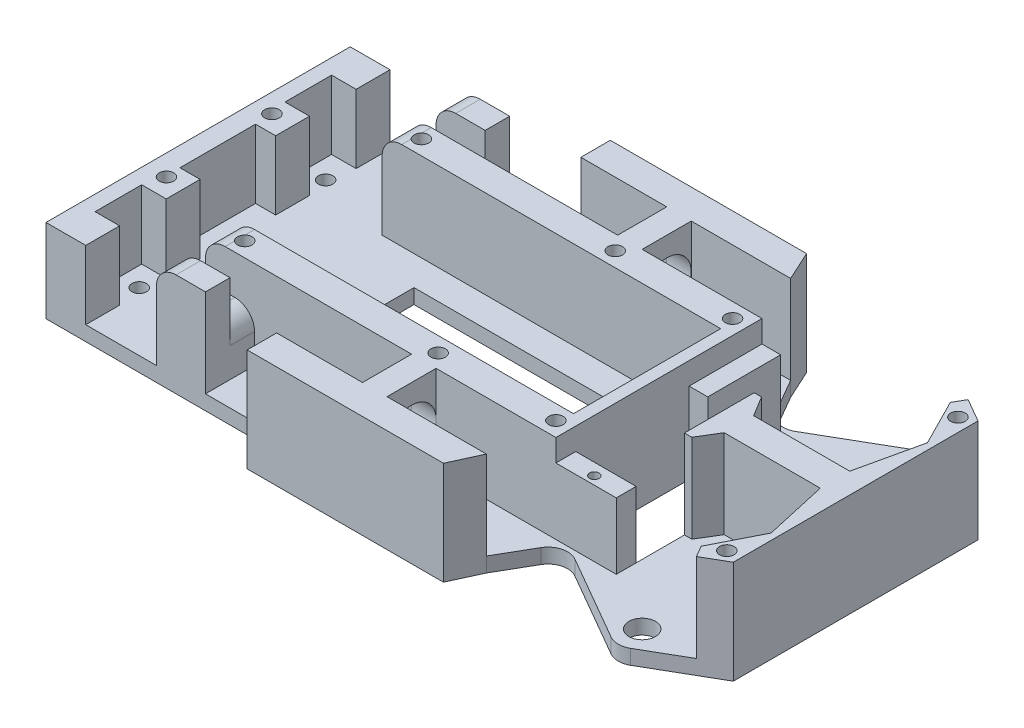
SolidWorks part; units mm, degrees
ref_plane "前视基准面" through (0, 0, 0) normal (0, 0, 1) x (1, 0, 0)
ref_plane "上视基准面" through (0, 0, 0) normal (0, 1, 0) x (1, 0, 0)
ref_plane "右视基准面" through (0, 0, 0) normal (1, 0, 0) x (0, 0, -1)
sketch "草图1" plane through (0, 0, 0) normal (0, 1, 0) x (1, 0, 0)
  line L0 (-67, 0) -> (67, 0) construction
  line L1 (-67, 31) -> (67, 31)
  line L2 (-67, 31) -> (-67, -31)
  line L3 (-67, -31) -> (67, -31)
  line L4 (67, 31) -> (67, -31)
  line L5 (-67, 31) -> (67, -31) construction
  line L6 (-67, -31) -> (67, 31) construction
  line L7 (0, -31) -> (0, 31) construction
  line L8 (22.7513, 31) -> (28.8135, 20.5)
  line L10 (-67, 1) -> (-67, -1)
  line L12 (67, 1) -> (67, -1)
  line L13 (-67, 1) -> (67, -1) construction
  line L14 (-67, -1) -> (67, 1) construction
  line L15 (-1, 31) -> (1, 31)
  line L17 (-1, -31) -> (1, -31)
  line L19 (-1, 31) -> (1, -31) construction
  line L20 (-1, -31) -> (1, 31) construction
  line L27 (28.8135, 20.5) -> (47, 31)
  line L28 (22.7513, -31) -> (28.8135, -20.5)
  line L29 (28.8135, -20.5) -> (47, -31)
  line L30 (56.5, -31) -> (67, -24.9378)
  line L31 (56.5, 31) -> (67, 24.9378)
  line L32 (56.5, 31) -> (51.75, 33.7424)
  line L33 (51.75, 33.7424) -> (47, 31)
  line L34 (51.75, -33.7424) -> (47, -31)
  line L35 (56.5, -31) -> (51.75, -33.7424)
  line L40 (26.9153, 6.15) -> (26.9153, -16.95)
  line L41 (26.9153, -16.95) -> (39.2153, -16.95)
  line L42 (39.2153, -16.95) -> (39.2153, 6.15)
  line L43 (39.2153, 6.15) -> (26.9153, 6.15)
  line L44 (26.9153, 6.15) -> (26.9153, -16.95)
  line L45 (26.9153, -16.95) -> (39.2153, -16.95)
  line L46 (39.2153, -16.95) -> (39.2153, 6.15)
  line L47 (39.2153, 6.15) -> (26.9153, 6.15)
  point P0 (0, 0)
  point P6 (0, 0)
  point P9 (0, 0)
  point P12 (0, 0)
  point P17 (0, 0)
  point P22 (0, 0)
  dimension "D1" = 134
  dimension "D2" = 62
  dimension "D7" = 6.15
  dimension "D8" = 30
  dimension "D9" = 20
  dimension "D10" = 90
  dimension "D11" = 21
  dimension "D12" = 30
  dimension "D13" = 10.5
  dimension "D14" = 30
  dimension "D15" = 30
  dimension "D16" = 0
extrude "凸台-拉伸1" add sketch "草图1" along normal blind 3 contours L1 L2 | L1 L4 | L3 L4 | L2 L1 L4 L3 region at (-2.8294, 0, -0.1991) region at (63.5, 0, -28.9793) region at (63.5, 0, 28.9793)
sketch "草图2" plane through (0, 3, 0) normal (0, 1, 0) x (1, 0, 0)
  line L0 (67, 31) -> (67, -31) construction
  line L1 (-67, 31) -> (67, 31) construction
  line L2 (67, 31) -> (67, -31) construction
  line L3 (-67, -31) -> (67, -31) construction
  circle A0 centre (51.5, 28) radius 2.7
  circle A1 centre (51.5, -28) radius 2.7
  dimension "D1" = 15.5
  dimension "D3" = 15.5
  dimension "D5" = 5.4
  dimension "D6" = 5.4
  dimension "D2" = 3
  dimension "D4" = 3
extrude "切除-拉伸1" cut sketch "草图2" against normal blind 4
extrude "凸台-拉伸3" add sketch "草图1<4>" along normal blind 3 contours L32 L33 L1 | L35 L3 L34 region at (51.75, 0, -31.9141) region at (51.75, 0, 31.9141)
sketch "草图1<4>" plane through (0, 0, 0) normal (0, 1, 0) x (1, 0, 0) same geometry as "草图1"
extrude "切除-拉伸4" cut sketch "草图1<6>" against normal blind 3 and the other way blind 4 contours L46 L47 L44 L45 | L8 L27 L1 | L1 L31 L4 | L29 L28 L3 | L30 L3 L4 region at (32.8549, 0, -27.5) region at (63.5, 0, -28.9793) region at (32.8549, 0, 27.5) region at (63.5, 0, 28.9793) region at (33.0653, 0, 5.4)
sketch "草图1<6>" plane through (0, 0, 0) normal (0, 1, 0) x (1, 0, 0) same geometry as "草图1"
sketch "草图3" plane through (0, 3, 0) normal (0, 1, 0) x (1, 0, 0)
  line L0 (-67, 0) -> (67, 0) construction
  line L1 (-67, 31) -> (-58.9, 31)
  line L2 (-67, 31) -> (-67, 7.7)
  line L3 (-67, 7.7) -> (-58.9, 7.7)
  line L4 (-58.9, 31) -> (-58.9, 7.7)
  line L5 (-67, -31) -> (-58.9, -31)
  line L6 (-67, -31) -> (-67, -7.7)
  line L7 (-67, -7.7) -> (-58.9, -7.7)
  line L8 (-58.9, -31) -> (-58.9, -7.7)
  line L9 (-67, 31) -> (-67, -31) construction
  line L10 (67, 24.9378) -> (67, -24.9378) construction
  line L12 (-58.9, 24.1) -> (-63.9, 24.1)
  line L13 (-58.9, 24.1) -> (-58.9, 14.6)
  line L14 (-58.9, 14.6) -> (-63.9, 14.6)
  line L15 (-63.9, 24.1) -> (-63.9, 14.6)
  line L16 (-58.9, -14.6) -> (-63.9, -14.6)
  line L17 (-58.9, -14.6) -> (-58.9, -24.1)
  line L18 (-58.9, -24.1) -> (-63.9, -24.1)
  line L19 (-63.9, -14.6) -> (-63.9, -24.1)
  line L20 (-67, 7.7) -> (-63, 7.7)
  line L21 (-67, 7.7) -> (-67, -7.7)
  line L22 (-67, -7.7) -> (-63, -7.7)
  line L23 (-63, 7.7) -> (-63, -7.7)
  line M12 (22.7513, 31) -> (-67, 31)
  line M13 (-67, 31) -> (-67, -31)
  line M14 (-67, -31) -> (22.7513, -31)
  dimension "D1" = 8.1
  dimension "D2" = 23.3
  dimension "D3" = 8.1
  dimension "D4" = 23.3
  dimension "D5" = 5
  dimension "D6" = 6.9
  dimension "D7" = 6.9
  dimension "D8" = 5
  dimension "D9" = 6.9
  dimension "D10" = 6.9
  dimension "D11" = 4
extrude "凸台-拉伸4" add sketch "草图3" along normal blind 14 contours L15 L12 L4 L3 L14 M12 M13 | L19 L16 L8 L7 L18 M13 M14 | L21 L20 L23 L22 region at (-62.95, 3, -30.7533) region at (-65, 3, 7.9467)
sketch "草图4" plane through (0, 3, 0) normal (0, 1, 0) x (1, 0, 0)
  line L0 (-67, 0) -> (67, 0) construction
  line L1 (67, 24.9378) -> (67, -24.9378) construction
  line L2 (-44.5, 9.7) -> (-44.5, 21) construction
  line L3 (-44.5, 21) -> (24.5, 21)
  line L4 (-44.5, 21) -> (-44.5, 15)
  line L5 (-44.5, 15) -> (24.5, 15)
  line L6 (24.5, 21) -> (24.5, 15)
  line L7 (-44.5, -15) -> (24.5, -15)
  line L8 (24.5, -21) -> (24.5, -15)
  line L9 (-44.5, -21) -> (24.5, -21)
  line L10 (-44.5, -21) -> (-44.5, -15)
  line L11 (26.9153, -21.7) -> (26.9153, -16.95) construction
  line L12 (24.5, 21) -> (26.9153, 21)
  line L13 (24.5, 21) -> (24.5, -21)
  line L14 (24.5, -21) -> (26.9153, -21)
  line L15 (26.9153, 21) -> (26.9153, -21)
  line L26 (-58.9, 31) -> (22.7513, 31) construction
  line L35 (-44.5, 31) -> (-34.5, 31)
  line L36 (-44.5, 31) -> (-44.5, 26)
  line L37 (-44.5, 26) -> (-34.5, 26)
  line L38 (-34.5, 31) -> (-34.5, 26)
  line L39 (-34.5, -21) -> (-39.5, -21)
  line L40 (-34.5, 26) -> (-39.5, 26)
  line L41 (-34.5, 26) -> (-34.5, 21)
  line L42 (-34.5, 21) -> (-39.5, 21)
  line L43 (-39.5, 26) -> (-39.5, 21)
  line L44 (-39.5, -26) -> (-39.5, -21)
  line L45 (-34.5, -26) -> (-39.5, -26)
  line L46 (-34.5, -26) -> (-34.5, -21)
  line L47 (-44.5, -26) -> (-34.5, -26)
  line L48 (-34.5, -31) -> (-34.5, -26)
  line L49 (-44.5, -31) -> (-34.5, -31)
  line L50 (-44.5, -31) -> (-44.5, -26)
  point P6 (0, 0)
  line M11 (26.9153, -16.95) -> (26.9153, 6.15)
  dimension "D1" = 15
  dimension "D2" = 6
  dimension "D3" = 69
  dimension "D4" = 5
  dimension "D5" = 10
  dimension "D6" = 5
  dimension "D7" = 5
extrude "凸台-拉伸5" add sketch "草图4" along normal blind 18 contours L13 L0 L15 L12 L6 | L6 L3 L4 L5 | L10 L9 L8 L7 | L0 L13 L8 L14 L15 M11 | L38 L35 L36 L37 | L41 L40 L43 L42 | L46 L39 L44 L45 | L48 L49 L50 L47 region at (25.7076, 3, -10.5) region at (25.7076, 3, 10.5) region at (-10, 3, -18) region at (-10, 3, 18)
fillet "圆角1" radius 4 4 edges at (51.75, 1.5, 33.7424) (51.75, 1.5, -33.7424) (28.8135, 1.5, -20.5) (28.8135, 1.5, 20.5)
sketch "草图5" plane through (0, 3, 0) normal (0, 1, 0) x (1, 0, 0)
  line L0 (-67, 0) -> (67, 0) construction
  line L1 (67, 24.9378) -> (67, -24.9378) construction
  line L2 (39.2153, 6.15) -> (39.2153, -16.95) construction
  line L3 (39.2153, 3) -> (67, 3)
  line L4 (39.2153, 3) -> (39.2153, -3)
  line L5 (39.2153, -3) -> (67, -3)
  line L6 (67, 3) -> (67, -3)
  line L7 (43.2153, 3) -> (40.7153, 7.103)
  line L8 (39.2153, 3) -> (43.2153, 3)
  line L9 (39.2153, 3) -> (39.2153, 7.103)
  line L10 (39.2153, 7.103) -> (43.2153, 7.103) construction
  line L11 (43.2153, 3) -> (43.2153, 7.103) construction
  line L12 (40.7153, 7.103) -> (39.2153, 7.103)
  line L13 (39.2153, -3) -> (39.2153, -7.103)
  line L14 (40.7153, -7.103) -> (39.2153, -7.103)
  line L15 (43.2153, -3) -> (40.7153, -7.103)
  line L16 (39.2153, -3) -> (43.2153, -3)
  point P6 (0, 0)
  line M11 (67, -24.9378) -> (67, 24.9378)
  line M37 (39.2153, 6.15) -> (39.2153, -16.95)
  dimension "D1" = 6
  dimension "D2" = 3
  dimension "D3" = 4
  dimension "D4" = 1.5
extrude "凸台-拉伸6" add sketch "草图5" along normal blind 18 contours L5 L3 M37 M11 | L7 L12 L9 L3 M37 | L15 L5 L14 M37 region at (40.6849, 3, -4.7406) region at (53.1076, 3, 0) region at (40.6849, 3, 4.7406)
sketch "草图6" plane through (0, 3, 0) normal (0, 1, 0) x (1, 0, 0)
  line L1 (39.2153, -16.95) -> (26.9153, -16.95)
  line L2 (39.2153, -16.95) -> (39.2153, -21)
  line L3 (39.2153, -21) -> (26.9153, -21)
  line L4 (26.9153, -16.95) -> (26.9153, -21)
  line L11 (26.9153, 6.15) -> (39.2153, 6.15) construction
  line L12 (26.9153, 21) -> (30.7153, 21)
  line L13 (26.9153, 21) -> (26.9153, 6.15)
  line L14 (26.9153, 6.15) -> (30.7153, 6.15)
  line L15 (30.7153, 21) -> (30.7153, 6.15)
  line L16 (30.7153, 19.15) -> (30.7153, 6.15) construction
extrude "凸台-拉伸7" add sketch "草图6" along normal blind 13.5
sketch "草图7" plane through (0, 0, 0) normal (0, -1, 0) x (1, 0, 0)
  line L0 (-67, 0) -> (67, 0) construction
  line L1 (67, -24.9378) -> (67, 24.9378) construction
  line L2 (-67, -31) -> (-67, 31) construction
  line L3 (-67, 31) -> (22.7513, 31) construction
  circle A0 centre (-60, 19) radius 1.48
  circle A1 centre (-43, 23.5) radius 1.48
  circle A2 centre (-43, -23.5) radius 1.48
  circle A3 centre (-60, -19) radius 1.48
  point P8 (0, 0)
  dimension "D1" = 7
  dimension "D3" = 24
  dimension "D8" = 2.96
  dimension "D9" = 2.96
  dimension "D2" = 12
  dimension "D4" = 7.5
extrude "切除-拉伸5" cut sketch "草图7" against normal blind 5
sketch "草图9" plane through (0, 3, 0) normal (0, 1, 0) x (1, 0, 0)
  line L0 (67, 15.9378) -> (65.7, 15.9378)
  line L1 (67, 24.9378) -> (67, 3) construction
  line L2 (65.7, 15.9378) -> (58.7, 29.7298)
  line L4 (65.7, 15.9378) -> (62.8, 3)
  line L5 (43.2153, 3) -> (67, 3) construction
  line L6 (62.8, 3) -> (67, 3)
  line L7 (67, 3) -> (67, 15.9378)
  line L9 (67, 24.9378) -> (53.75, 32.5877) construction
  line L10 (65.7, 15.9378) -> (67, 15.9378)
  line L12 (58.7, 29.7298) -> (67, 24.9378)
  line L13 (67, 24.9378) -> (67, 15.9378)
  line L14 (67, -3) -> (67, 3) construction
  line L15 (62.2369, 27.6878) -> (60.9062, 25.383)
  point P17 (66.35, 15.9378)
  line M14 (43.2153, 3) -> (67, 3)
  line M15 (67, 3) -> (67, 24.9378)
  line M16 (67, 24.9378) -> (53.75, 32.5877)
  dimension "D1" = 8.3
  dimension "D2" = 1.3
  dimension "D3" = 4.2
  dimension "D4" = 9
  dimension "D5" = 5.5
extrude "凸台-拉伸9" add sketch "草图9" along normal blind 18 contours L0 L4 M14 M15 | L2 L0 M15 M16 region at (65.4976, 3, -8.332) region at (64.6194, 3, -22.3369)
sketch "草图10" plane through (0, 3, 0) normal (0, 1, 0) x (1, 0, 0)
  line L0 (67, -3) -> (62.8, -3)
  line L1 (43.2153, -3) -> (67, -3) construction
  line L2 (62.8, -3) -> (65.7, -15.9378)
  line L3 (65.7, -15.9378) -> (67, -15.9378)
  line L4 (67, -3) -> (67, -24.9378) construction
  line L5 (67, -15.9378) -> (67, -24.9378)
  line L6 (67, -24.9378) -> (58.7, -29.7298)
  line L7 (67, -24.9378) -> (53.75, -32.5877) construction
  line L8 (58.7, -29.7298) -> (65.7, -15.9378)
  line L9 (67, -3) -> (67, -15.9378)
  line L10 (62.2369, -27.6878) -> (60.9062, -25.383)
  line M19 (67, -24.9378) -> (67, -3)
  line M20 (67, -3) -> (43.2153, -3)
  dimension "D1" = 9
  dimension "D2" = 1.3
  dimension "D3" = 8.3
  dimension "D4" = 4.2
  dimension "D5" = 90
  dimension "D6" = 5.5
extrude "凸台-拉伸10" add sketch "草图10" along normal blind 18 contours L10 L6 L3 L8 M19 | L2 L3 M19 M20 region at (65.4976, 3, 8.332) region at (64.6194, 3, 22.3369)
sketch "草图11" plane through (0, 0, 0) normal (0, -1, 0) x (1, 0, 0)
  line L0 (-34.5, -31) -> (22.7513, -31) construction
  line L1 (-20, -31) -> (20, -31)
  line L2 (-20, -31) -> (-20, -37)
  line L3 (-20, -37) -> (20, -37)
  line L4 (20, -31) -> (20, -37)
  line L5 (-67, -31) -> (-67, 31) construction
  line L6 (67, 24.9378) -> (67, -24.9378) construction
  line L7 (20, -37) -> (22.7513, -31)
  line L8 (22.7513, -31) -> (20, -31)
  line L9 (0, 0) -> (67, 0) construction
  line L10 (22.7513, 31) -> (20, 31)
  line L11 (20, 37) -> (22.7513, 31)
  line L12 (20, 31) -> (20, 37)
  line L13 (-20, 37) -> (20, 37)
  line L14 (-20, 31) -> (-20, 37)
  line L15 (-20, 31) -> (20, 31)
  line L16 (-34.5, -21) -> (26.9153, -21) construction
  line L17 (-2.5, -31) -> (2.5, -31)
  line L18 (-2.5, -31) -> (-2.5, -21)
  line L19 (-2.5, -21) -> (2.5, -21)
  line L20 (2.5, -31) -> (2.5, -21)
  line L21 (-2.5, 21) -> (2.5, 21)
  line L22 (-2.5, 31) -> (-2.5, 21)
  line L23 (2.5, 31) -> (2.5, 21)
  line M25 (22.7513, 31) -> (-67, 31)
  line M27 (-67, -31) -> (22.7513, -31)
  dimension "D1" = 47
  dimension "D2" = 47
  dimension "D3" = 6
  dimension "D4" = 5
  dimension "D5" = 2.5
extrude "凸台-拉伸11" add sketch "草图11" against normal up to surface (21 mm away) contours L4 L1 L2 L3 M27 | L1 L20 L19 L18 | L4 L7 M27 | L14 L15 L12 L13 M25 | L23 L15 L22 L21 | L12 L11 M25 region at (0, 0, -34) region at (0, 0, -26) region at (20.9171, 0, -33) region at (20.9171, 0, 33) region at (0, 0, 34) region at (0, 0, 26) up to face at (-27.4585, 21, 0)
sketch "草图12" plane through (-2.5, 0, 0) normal (-1, 0, 0) x (0, 0, 1)
  line L0 (26, 3) -> (26, 21) construction
  line L1 (31, 12) -> (21, 12) construction
  line L4 (21, 21) -> (21, 3)
  line L5 (21, 3) -> (31, 3)
  line L6 (31, 3) -> (31, 21)
  line L7 (31, 21) -> (21, 21)
  line L8 (21, 21) -> (21, 3)
  line L9 (21, 3) -> (31, 3)
  line L10 (31, 3) -> (31, 21)
  line L11 (31, 21) -> (21, 21)
  circle A0 centre (26, 12) radius 5
  dimension "D2" = 10
  dimension "D1" = 0
extrude "切除-拉伸6" cut sketch "草图12" against normal blind 6 contours A0
sketch "草图13" plane through (-2.5, 0, 0) normal (-1, 0, 0) x (0, 0, 1)
  line L0 (-21, 12) -> (-31, 12) construction
  line L1 (-26, 3) -> (-26, 21) construction
  line L4 (-31, 3) -> (-21, 3)
  line L5 (-21, 3) -> (-21, 21)
  line L6 (-21, 21) -> (-31, 21)
  line L7 (-31, 21) -> (-31, 3)
  line L8 (-31, 3) -> (-21, 3)
  line L9 (-21, 3) -> (-21, 21)
  line L10 (-21, 21) -> (-31, 21)
  line L11 (-31, 21) -> (-31, 3)
  circle A0 centre (-26, 12) radius 5
  dimension "D2" = 10
  dimension "D1" = 0
extrude "切除-拉伸7" cut sketch "草图13" against normal blind 6 contours A0 | A0 region at (-2.5, 12, -26)
sketch "草图14" plane through (0, 16.5, 0) normal (0, 1, 0) x (1, 0, 0)
  line L0 (26.9153, -21) -> (26.9153, 21) construction
  line L1 (39.2153, -16.95) -> (26.9153, -16.95) construction
  circle A0 centre (33.0653, -19.325) radius 0.965 construction
  circle A1 centre (33.0653, -19.325) radius 0.965
  dimension "D1" = 6.15
  dimension "D2" = 2.375
extrude "切除-拉伸8" cut sketch "草图14" against normal blind 10 contours A1
sketch "草图17" plane through (0, 21, 0) normal (0, 1, 0) x (1, 0, 0)
  line L16 (39.2153, 7.103) -> (39.2153, -7.103)
  line L17 (39.2153, -7.103) -> (40.7153, -7.103)
  line L18 (40.7153, -7.103) -> (43.2153, -3)
  line L19 (43.2153, -3) -> (62.8, -3)
  line L20 (62.8, -3) -> (65.7, -15.9378)
  line L21 (65.7, -15.9378) -> (60.9062, -25.383)
  line L22 (60.9062, -25.383) -> (62.2369, -27.6878)
  line L23 (62.2369, -27.6878) -> (67, -24.9378)
  line L24 (67, -24.9378) -> (67, 24.9378)
  line L25 (67, 24.9378) -> (62.2369, 27.6878)
  line L26 (62.2369, 27.6878) -> (60.9062, 25.383)
  line L27 (60.9062, 25.383) -> (65.7, 15.9378)
  line L28 (65.7, 15.9378) -> (62.8, 3)
  line L29 (62.8, 3) -> (43.2153, 3)
  line L30 (43.2153, 3) -> (40.7153, 7.103)
  line L31 (40.7153, 7.103) -> (39.2153, 7.103)
  line L32 (39.2153, 7.103) -> (39.2153, -7.103)
  line L33 (39.2153, -7.103) -> (40.7153, -7.103)
  line L34 (40.7153, -7.103) -> (43.2153, -3)
  line L35 (43.2153, -3) -> (62.8, -3)
  line L36 (62.8, -3) -> (65.7, -15.9378)
  line L37 (65.7, -15.9378) -> (60.9062, -25.383)
  line L38 (60.9062, -25.383) -> (62.2369, -27.6878)
  line L39 (62.2369, -27.6878) -> (67, -24.9378)
  line L40 (67, -24.9378) -> (67, 24.9378)
  line L41 (67, 24.9378) -> (62.2369, 27.6878)
  line L42 (62.2369, 27.6878) -> (60.9062, 25.383)
  line L43 (60.9062, 25.383) -> (65.7, 15.9378)
  line L44 (65.7, 15.9378) -> (62.8, 3)
  line L45 (62.8, 3) -> (43.2153, 3)
  line L46 (43.2153, 3) -> (40.7153, 7.103)
  line L47 (40.7153, 7.103) -> (39.2153, 7.103)
  circle A0 centre (64.3, 23.55) radius 1.48 construction
  circle A1 centre (64.3, 23.55) radius 1.48
  circle A2 centre (64.3, -23.55) radius 1.48 construction
  circle A3 centre (64.3, -23.55) radius 1.48
  dimension "D1" = 0
extrude "切除-拉伸10" cut sketch "草图17" against normal blind 30 contours A1 | A3
sketch "草图18" plane through (0, 21, 0) normal (0, 1, 0) x (1, 0, 0)
  circle A0 centre (23.9153, 18) radius 1.48 construction
  circle A1 centre (23.9153, 18) radius 1.48
  circle A2 centre (23.9153, -18) radius 1.48 construction
  circle A3 centre (23.9153, -18) radius 1.48
extrude "切除-拉伸11" cut sketch "草图18" against normal blind 30
sketch "草图19" plane through (0, 21, 0) normal (0, 1, 0) x (1, 0, 0)
  line L0 (-44.5, 15) -> (24.5, 15) construction
  line L1 (-39.5919, -15.0759) -> (24.4081, -15.0759) construction
  circle A0 centre (0, 18) radius 1.48
  circle A1 centre (0, -18.0759) radius 1.48
  dimension "D1" = 3
  dimension "D2" = 3
extrude "切除-拉伸12" cut sketch "草图19" against normal blind 30
sketch "草图20" plane through (0, 21, 0) normal (0, 1, 0) x (1, 0, 0)
  line L0 (-34.5, -31) -> (-34.5, -21) construction
  line L1 (-39.5, 26) -> (-34.5, 26)
  line L2 (-39.5, 26) -> (-39.5, 21)
  line L3 (-39.5, 21) -> (-34.5, 21)
  line L4 (-34.5, 26) -> (-34.5, 21)
  line L5 (-39.5, -21) -> (-34.5, -21)
  line L6 (-39.5, -21) -> (-39.5, -26)
  line L7 (-39.5, -26) -> (-34.5, -26)
  line L8 (-34.5, -21) -> (-34.5, -26)
extrude "切除-拉伸13" cut sketch "草图20" against normal blind 8
sketch "草图21" plane through (0, 21, 0) normal (0, 1, 0) x (1, 0, 0)
  line L24 (-2.5, 31) -> (-2.5, 21)
  line L25 (-2.5, 21) -> (-44.5, 21)
  line L26 (-44.5, 21) -> (-44.5, 15)
  line L27 (-44.5, 15) -> (24.5, 15)
  line L28 (24.5, 15) -> (24.5, -15)
  line L29 (24.5, -15) -> (-44.5, -15)
  line L30 (-44.5, -15) -> (-44.5, -21)
  line L31 (-44.5, -21) -> (-2.5, -21)
  line L32 (-2.5, -21) -> (-2.5, -31)
  line L33 (-2.5, -31) -> (-20, -31)
  line L34 (-20, -31) -> (-20, -37)
  line L35 (-20, -37) -> (20, -37)
  line L36 (20, -37) -> (22.7513, -31)
  line L37 (22.7513, -31) -> (2.5, -31)
  line L38 (2.5, -31) -> (2.5, -21)
  line L39 (2.5, -21) -> (26.9153, -21)
  line L40 (26.9153, -21) -> (26.9153, 21)
  line L41 (26.9153, 21) -> (2.5, 21)
  line L42 (2.5, 21) -> (2.5, 31)
  line L43 (2.5, 31) -> (22.7513, 31)
  line L44 (22.7513, 31) -> (20, 37)
  line L45 (20, 37) -> (-20, 37)
  line L46 (-20, 37) -> (-20, 31)
  line L47 (-20, 31) -> (-2.5, 31)
  line L48 (-2.5, 31) -> (-2.5, 21)
  line L49 (-2.5, 21) -> (-44.5, 21)
  line L50 (-44.5, 21) -> (-44.5, 15)
  line L51 (-44.5, 15) -> (24.5, 15)
  line L52 (24.5, 15) -> (24.5, -15)
  line L53 (24.5, -15) -> (-44.5, -15)
  line L54 (-44.5, -15) -> (-44.5, -21)
  line L55 (-44.5, -21) -> (-2.5, -21)
  line L56 (-2.5, -21) -> (-2.5, -31)
  line L57 (-2.5, -31) -> (-20, -31)
  line L58 (-20, -31) -> (-20, -37)
  line L59 (-20, -37) -> (20, -37)
  line L60 (20, -37) -> (22.7513, -31)
  line L61 (22.7513, -31) -> (2.5, -31)
  line L62 (2.5, -31) -> (2.5, -21)
  line L63 (2.5, -21) -> (26.9153, -21)
  line L64 (26.9153, -21) -> (26.9153, 21)
  line L65 (26.9153, 21) -> (2.5, 21)
  line L66 (2.5, 21) -> (2.5, 31)
  line L67 (2.5, 31) -> (22.7513, 31)
  line L68 (22.7513, 31) -> (20, 37)
  line L69 (20, 37) -> (-20, 37)
  line L70 (-20, 37) -> (-20, 31)
  line L71 (-20, 31) -> (-2.5, 31)
  circle A0 centre (-39.5, 18) radius 1.48
  circle A1 centre (-39.5, -18) radius 1.48
  dimension "D2" = 3
  dimension "D3" = 3
  dimension "D4" = 5
  dimension "D5" = 5
  dimension "D1" = 0
extrude "切除-拉伸14" cut sketch "草图21" against normal blind 30 contours A0 | A1
sketch "草图22" plane through (0, 17, 0) normal (0, 1, 0) x (1, 0, 0)
  line L8 (-63.9, 14.6) -> (-63.9, 24.1)
  line L9 (-63.9, 24.1) -> (-58.9, 24.1)
  line L10 (-58.9, 24.1) -> (-58.9, 31)
  line L11 (-58.9, 31) -> (-67, 31)
  line L12 (-67, 31) -> (-67, -31)
  line L13 (-63, 7.7) -> (-58.9, 7.7)
  line L14 (-58.9, 7.7) -> (-58.9, 14.6)
  line L15 (-58.9, 14.6) -> (-63.9, 14.6)
  line L16 (-63.9, 14.6) -> (-63.9, 24.1)
  line L17 (-63.9, 24.1) -> (-58.9, 24.1)
  line L18 (-58.9, 24.1) -> (-58.9, 31)
  line L19 (-58.9, 31) -> (-67, 31)
  line L20 (-67, 31) -> (-67, -31)
  line L21 (-63, 7.7) -> (-58.9, 7.7)
  line L22 (-58.9, 7.7) -> (-58.9, 14.6)
  line L23 (-58.9, 14.6) -> (-63.9, 14.6)
  line L32 (-67, -31) -> (-58.9, -31)
  line L33 (-67, -31) -> (-58.9, -31)
  line L34 (-58.9, -31) -> (-58.9, -24.1)
  line L35 (-58.9, -31) -> (-58.9, -24.1)
  line L36 (-58.9, -24.1) -> (-63.9, -24.1)
  line L37 (-58.9, -24.1) -> (-63.9, -24.1)
  line L38 (-63.9, -24.1) -> (-63.9, -14.6)
  line L39 (-63.9, -24.1) -> (-63.9, -14.6)
  line L40 (-63.9, -14.6) -> (-58.9, -14.6)
  line L41 (-63.9, -14.6) -> (-58.9, -14.6)
  line L42 (-58.9, -14.6) -> (-58.9, -7.7)
  line L43 (-58.9, -14.6) -> (-58.9, -7.7)
  line L44 (-58.9, -7.7) -> (-63, -7.7)
  line L45 (-58.9, -7.7) -> (-63, -7.7)
  line L46 (-63, -7.7) -> (-63, 7.7)
  line L47 (-63, -7.7) -> (-63, 7.7)
  circle A0 centre (-63.15, 11.2) radius 1.48
  dimension "D2" = 4.25
  dimension "D3" = 3.5
  dimension "D1" = 0
extrude "切除-拉伸15" cut sketch "草图22" against normal blind 30 contours A0
sketch "草图23" plane through (0, 17, 0) normal (0, 1, 0) x (1, 0, 0)
  line L8 (-63.9, -24.1) -> (-63.9, -14.6)
  line L9 (-63.9, -14.6) -> (-58.9, -14.6)
  line L10 (-58.9, -14.6) -> (-58.9, -7.7)
  line L11 (-58.9, -7.7) -> (-63, -7.7)
  line L12 (-67, 31) -> (-67, -31)
  line L13 (-67, -31) -> (-58.9, -31)
  line L14 (-58.9, -31) -> (-58.9, -24.1)
  line L15 (-58.9, -24.1) -> (-63.9, -24.1)
  line L16 (-63.9, -24.1) -> (-63.9, -14.6)
  line L17 (-63.9, -14.6) -> (-58.9, -14.6)
  line L18 (-58.9, -14.6) -> (-58.9, -7.7)
  line L19 (-58.9, -7.7) -> (-63, -7.7)
  line L20 (-67, 31) -> (-67, -31)
  line L21 (-67, -31) -> (-58.9, -31)
  line L22 (-58.9, -31) -> (-58.9, -24.1)
  line L23 (-58.9, -24.1) -> (-63.9, -24.1)
  line L32 (-63.9, 14.6) -> (-63.9, 24.1)
  line L33 (-63.9, 14.6) -> (-63.9, 24.1)
  line L34 (-63.9, 24.1) -> (-58.9, 24.1)
  line L35 (-63.9, 24.1) -> (-58.9, 24.1)
  line L36 (-58.9, 24.1) -> (-58.9, 31)
  line L37 (-58.9, 24.1) -> (-58.9, 31)
  line L38 (-58.9, 31) -> (-67, 31)
  line L39 (-58.9, 31) -> (-67, 31)
  line L40 (-63, -7.7) -> (-63, 7.7)
  line L41 (-63, -7.7) -> (-63, 7.7)
  line L42 (-63, 7.7) -> (-58.9, 7.7)
  line L43 (-63, 7.7) -> (-58.9, 7.7)
  line L44 (-58.9, 7.7) -> (-58.9, 14.6)
  line L45 (-58.9, 7.7) -> (-58.9, 14.6)
  line L46 (-58.9, 14.6) -> (-63.9, 14.6)
  line L47 (-58.9, 14.6) -> (-63.9, 14.6)
  circle A0 centre (-62.75, -10.7017) radius 1.48
  point P6 (-60.95, -7.7)
  dimension "D2" = 3.5
  dimension "D3" = 4.25
  dimension "D1" = 0
extrude "切除-拉伸16" cut sketch "草图23" against normal blind 30 contours A0
sketch "草图24" plane through (0, 3, 0) normal (0, 1, 0) x (1, 0, 0)
  line L1 (-32, 9) -> (18, 9)
  line L2 (-32, 9) -> (-32, -9)
  line L3 (-32, -9) -> (18, -9)
  line L4 (18, 9) -> (18, -9)
  line L6 (-67, 7.7) -> (-67, -7.7) construction
  line L7 (-58.9, 31) -> (-44.5, 31) construction
  point P8 (-51.7, 31)
  dimension "D1" = 18
  dimension "D2" = 50
  dimension "D3" = 35
  dimension "D4" = 22
extrude "切除-拉伸17" cut sketch "草图24" against normal blind 30 contours L2 L1 L4 L3
fillet "圆角2" radius 4 4 edges at (-44.5, 21, -28.5) (-44.5, 21, -18) (-44.5, 21, 28.5) (-44.5, 21, 18)
fillet "圆角3" radius 4 2 edges at (-34.5, 13, 23.5) (-34.5, 13, -23.5)
